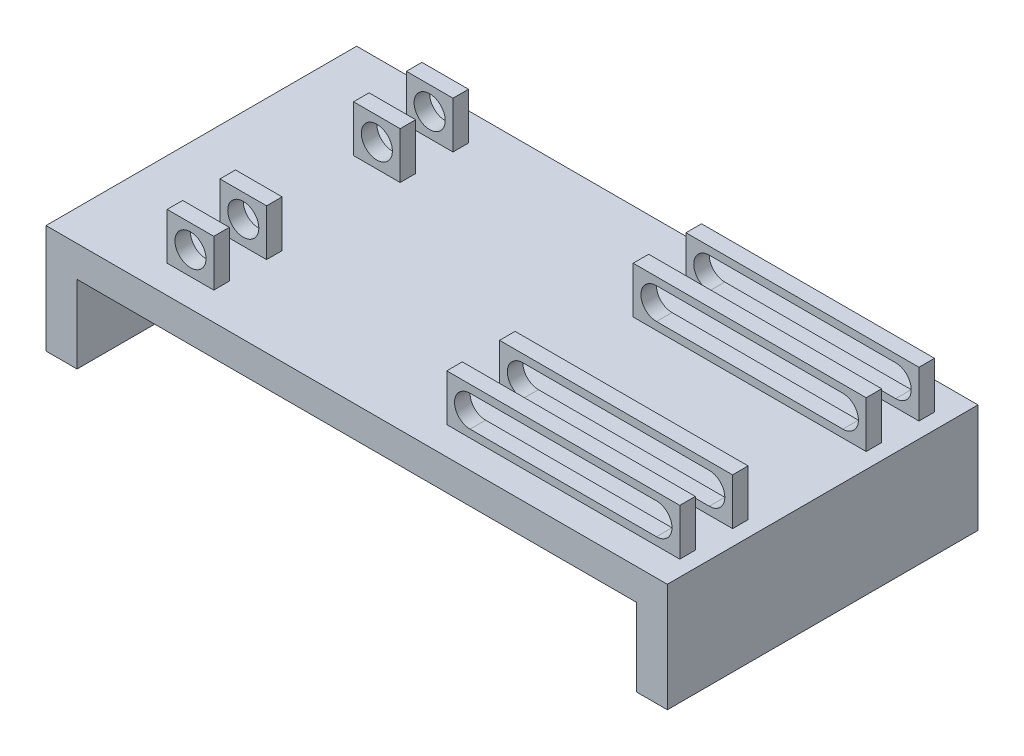
SolidWorks part; units mm, degrees
ref_plane "Front Plane" through (0, 0, 0) normal (0, 0, 1) x (1, 0, 0)
ref_plane "Top Plane" through (0, 0, 0) normal (0, 1, 0) x (1, 0, 0)
ref_plane "Right Plane" through (0, 0, 0) normal (1, 0, 0) x (0, 0, -1)
sketch "Sketch1" plane through (0, 0, 0) normal (0, 1, 0) x (1, 0, 0)
  line L0 (-100, -30) -> (100, -30) construction
  line L1 (-100, 50) -> (100, 50)
  line L2 (-100, 50) -> (-100, -50)
  line L3 (-100, -50) -> (100, -50)
  line L4 (100, 50) -> (100, -50)
  line L5 (-100, 50) -> (100, -50) construction
  line L6 (-100, -50) -> (100, 50) construction
  line L7 (95, -41) -> (20, -41)
  line L8 (-70, -36) -> (-55, -36)
  line L9 (-70, -19) -> (-55, -19)
  line L10 (-70, -19) -> (-70, -24)
  line L11 (-70, -24) -> (-55, -24)
  line L12 (-55, -19) -> (-55, -24)
  line L13 (-55, -41) -> (-55, -36)
  line L14 (-70, -41) -> (-55, -41)
  line L15 (-70, -41) -> (-70, -36)
  line L24 (95, -24) -> (20, -24)
  line L25 (95, -24) -> (95, -19)
  line L26 (95, -19) -> (20, -19)
  line L27 (20, -24) -> (20, -19)
  line L28 (95, -24) -> (20, -19) construction
  line L29 (95, -19) -> (20, -24) construction
  line L30 (20, -36) -> (20, -41)
  line L31 (95, -36) -> (20, -36)
  line L32 (95, -36) -> (95, -41)
  line L33 (-100, 0) -> (100, 0) construction
  line L34 (95, 19) -> (20, 19)
  line L35 (20, 24) -> (20, 19)
  line L36 (95, 24) -> (20, 24)
  line L37 (95, 24) -> (95, 19)
  line L38 (95, 36) -> (95, 41)
  line L39 (95, 36) -> (20, 36)
  line L40 (20, 36) -> (20, 41)
  line L41 (95, 41) -> (20, 41)
  line L42 (-70, 41) -> (-70, 36)
  line L43 (-70, 41) -> (-55, 41)
  line L44 (-55, 41) -> (-55, 36)
  line L45 (-70, 36) -> (-55, 36)
  line L46 (-70, 24) -> (-55, 24)
  line L47 (-55, 19) -> (-55, 24)
  line L48 (-70, 19) -> (-55, 19)
  line L49 (-70, 19) -> (-70, 24)
  point P0 (0, 0)
  point P8 (57.5, -21.5)
  point P25 (95, -38.5)
  dimension "D1" = 100
  dimension "D2" = 200
  dimension "D3" = 5
  dimension "D4" = 5
  dimension "D5" = 6
  dimension "D6" = 15
  dimension "D7" = 5
  dimension "D8" = 75
  dimension "D9" = 6
  dimension "D10" = 30
  dimension "D11" = 20
extrude "Boss-Extrude2" add sketch "Sketch1" along normal blind 10
extrude "Boss-Extrude3" add sketch "Sketch1<8>" along normal blind 25 contours L49 L48 L47 L46 | L42 L45 L44 L43 | L38 L41 L40 L39 | L37 L36 L35 L34 | L9 L12 L11 L10 | L8 L13 L14 L15 | L24 L27 L26 L25 | L31 L30 L7 L32 region at (57.5, 0, -21.5) region at (57.5, 0, -38.5) region at (-62.5, 0, -38.5) region at (-62.5, 0, -21.5)
sketch "Sketch1<8>" plane through (0, 0, 0) normal (0, 1, 0) x (1, 0, 0) same geometry as "Sketch1"
sketch "Sketch5" plane through (0, 0, 0) normal (0, -1, 0) x (1, 0, 0)
  line L0 (100, -50) -> (-100, -50) construction
  line L1 (-100, 50) -> (-90, 50)
  line L2 (-100, 50) -> (-100, -50)
  line L3 (-100, -50) -> (-90, -50)
  line L4 (-90, 50) -> (-90, -50)
  line L6 (100, 50) -> (90, 50)
  line L7 (100, 50) -> (100, -50)
  line L8 (100, -50) -> (90, -50)
  line L9 (90, 50) -> (90, -50)
  dimension "D1" = 10
  dimension "D2" = 10
extrude "Boss-Extrude4" add sketch "Sketch5" along normal blind 25
sketch "Sketch7" plane through (0, 0, 19) normal (0, 0, -1) x (-1, 0, 0)
  line L0 (55, 25) -> (70, 10) construction
  line L1 (70, 25) -> (55, 10) construction
  circle A0 centre (62.5, 17.5) radius 5
  dimension "D1" = 10
extrude "Cut-Extrude2" cut sketch "Sketch7" against normal through all both and the other way through all
sketch "Sketch8" plane through (0, 0, 41) normal (0, 0, 1) x (1, 0, 0)
  line L0 (27.5, 17.5) -> (87.5, 17.5) construction
  line L1 (27.5, 22.5) -> (87.5, 22.5)
  line L2 (27.5, 12.5) -> (87.5, 12.5)
  line L3 (95, 25) -> (20, 25) construction
  line L4 (95, 25) -> (95, 10) construction
  line L5 (20, 25) -> (20, 10) construction
  arc A0 (27.5, 22.5) -> (27.5, 12.5) centre (27.5, 17.5) ccw
  arc A1 (87.5, 12.5) -> (87.5, 22.5) centre (87.5, 17.5) ccw
  point P2 (57.5, 17.5)
  dimension "D2" = 5
  dimension "D1" = 7.5
  dimension "D3" = 7.5
  dimension "D4" = 7.5
extrude "Cut-Extrude3" cut sketch "Sketch8" against normal through all
